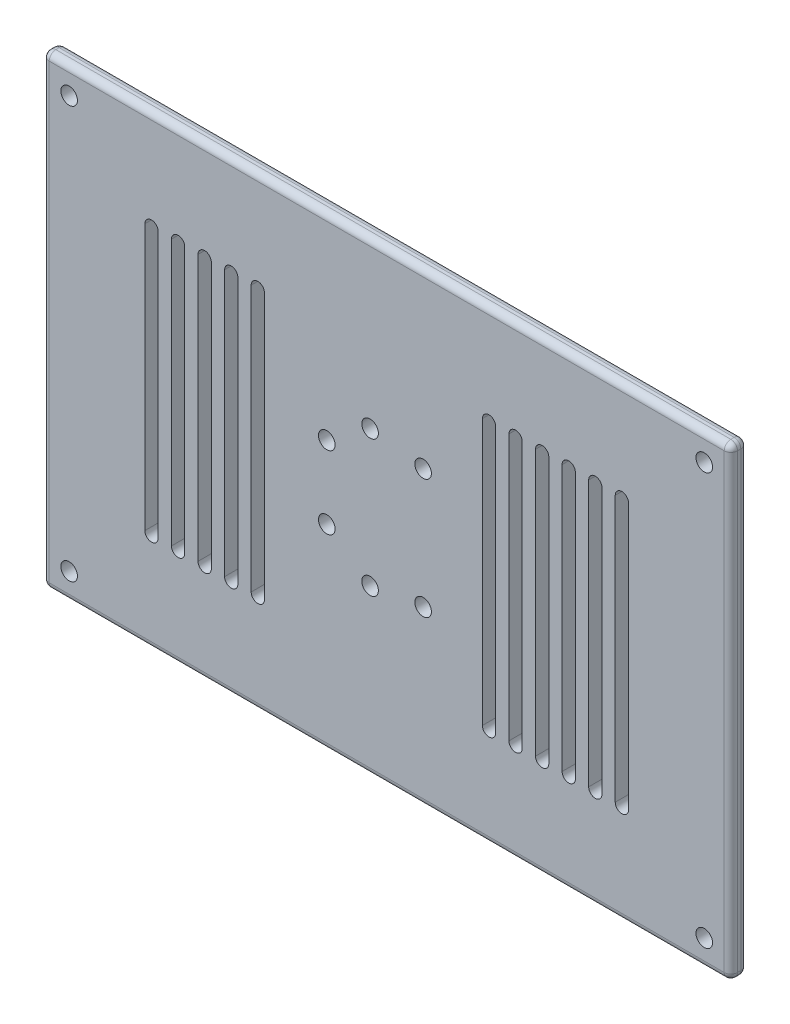
SolidWorks part; units mm, degrees
ref_plane "Plan de face" through (0, 0, 0) normal (0, 0, 1) x (1, 0, 0)
ref_plane "Plan de dessus" through (0, 0, 0) normal (0, 1, 0) x (1, 0, 0)
ref_plane "Plan de droite" through (0, 0, 0) normal (1, 0, 0) x (0, 0, -1)
sketch "Esquisse1" plane through (0, 0, 0) normal (0, 0, 1) x (1, 0, 0)
  line L1 (-51.8, 35) -> (51.8, 35)
  line L2 (-51.8, 35) -> (-51.8, -35)
  line L3 (-51.8, -35) -> (51.8, -35)
  line L4 (51.8, 35) -> (51.8, -35)
  line L5 (-51.8, 35) -> (51.8, -35) construction
  line L6 (-51.8, -35) -> (51.8, 35) construction
  point P0 (0, 0)
  point P5 (0, 0)
  point P13 (0, 0)
  dimension "D1" = 70
  dimension "D2" = 103.6
extrude "Boss.-Extru.1" add sketch "Esquisse1" along normal blind 2.5
sketch "Esquisse17" plane through (0, 0, 2.5) normal (0, 0, 1) x (1, 0, 0)
  line L1 (-2.5, 10.25) -> (2.5, 10.25)
  line L2 (-2.5, 10.25) -> (-2.5, -10.25) construction
  line L3 (-2.5, -10.25) -> (2.5, -10.25)
  line L4 (2.5, 10.25) -> (2.5, -10.25)
  line L5 (-2.5, 10.25) -> (2.5, -10.25) construction
  line L6 (-2.5, -10.25) -> (2.5, 10.25) construction
  circle A0 centre (-2.5, 10.25) radius 3
  circle A1 centre (-2.5, -10.25) radius 3
  point P0 (0, 0)
  point P9 (-2.5, -10.25)
  point P10 (-2.5, 10.25)
  dimension "D1" = 20.5
  dimension "D2" = 5
fillet "Congé3" radius 1 12 edges at (-51.8, 0, 2.5) (0, -35, 2.5) (0, 35, 2.5) (51.8, 0, 2.5) (51.8, -35, 1.25) (51.8, 35, 1.25) (-51.8, 35, 1.25) (-51.8, -35, 1.25) (51.8, 0, 0) (0, 35, 0) (-51.8, 0, 0) (0, -35, 0)
extrude "Boss.-Extru.12" add sketch "Esquisse17" against normal blind 7 contours A1 | A0
sketch "Esquisse40" plane through (0, 0, 2.5) normal (0, 0, 1) x (1, 0, 0)
  line L1 (9.0156, -5.4801) -> (5.4801, -9.0156)
  line L2 (9.0156, -5.4801) -> (-5.4801, 9.0156)
  line L3 (-5.4801, 9.0156) -> (-9.0156, 5.4801)
  line L4 (5.4801, -9.0156) -> (-9.0156, 5.4801)
  line L5 (2.5, -10.25) -> (-2.5, 10.25) construction
  line L6 (2.5, 10.25) -> (-2.5, -10.25) construction
  circle A0 centre (5.4801, -9.0156) radius 3
  circle A1 centre (-9.0156, 5.4801) radius 3
  point P0 (0, 0)
  dimension "D1" = 5
  dimension "D2" = 20.5
extrude "Boss.-Extru.8" add sketch "Esquisse40" against normal blind 7 contours A1 | A0
sketch "Esquisse42" plane through (0, 0, 2.5) normal (0, 0, 1) x (1, 0, 0)
  line L5 (-5.4801, -9.0156) -> (-9.0156, -5.4801)
  line L6 (-5.4801, -9.0156) -> (9.0156, 5.4801)
  line L7 (9.0156, 5.4801) -> (5.4801, 9.0156)
  line L8 (-9.0156, -5.4801) -> (5.4801, 9.0156)
  line L9 (2.5, -10.25) -> (-2.5, 10.25) construction
  line L10 (2.5, 10.25) -> (-2.5, -10.25) construction
  circle A0 centre (-9.0156, -5.4801) radius 3
  circle A1 centre (5.4801, 9.0156) radius 3
  point P0 (0, 0)
  dimension "D1" = 5
  dimension "D2" = 20.5
extrude "Boss.-Extru.10" add sketch "Esquisse42" against normal blind 7 contours A1 | A0
sketch "Esquisse36" plane through (0, 0, 2.5) normal (0, 0, 1) x (1, 0, 0)
  line L0 (25.4, 0) -> (0, 0) construction
  line L1 (50.8, -34) -> (50.8, 34) construction
  line L2 (50.8, 0) -> (25.4, 0) construction
  line L4 (35.4, -20) -> (15.4, -20) construction
  line L5 (35.4, -20) -> (35.4, 20) construction
  line L6 (35.4, 20) -> (15.4, 20) construction
  line L7 (15.4, -20) -> (15.4, 20) construction
  line L8 (35.4, -20) -> (15.4, 20) construction
  line L9 (35.4, 20) -> (15.4, -20) construction
  line L10 (35.4, 20) -> (35.4, -20) construction
  line L11 (36.4, 20) -> (36.4, -20)
  line L12 (34.4, 20) -> (34.4, -20)
  arc A0 (36.4, 20) -> (34.4, 20) centre (35.4, 20) ccw
  arc A1 (34.4, -20) -> (36.4, -20) centre (35.4, -20) ccw
  point P0 (25.4, 0)
  point P8 (35.4, 0)
  dimension "D1" = 20
  dimension "D2" = 40
extrude "Enlèv. mat.-Extru.2" cut sketch "Esquisse36" against normal through all
pattern_linear "Répétition linéaire1" count 6 spacing 4 along (-1, 0, 0) of "Enlèv. mat.-Extru.2"
sketch "Esquisse37" plane through (0, 0, 2.5) normal (0, 0, 1) x (1, 0, 0)
  line L0 (0, 0) -> (-50.8, 0) construction
  line L1 (-50.8, 34) -> (-50.8, -34) construction
  line L2 (-35.4, 20) -> (-35.4, -20) construction
  line L3 (-15.4, 20) -> (-35.4, 20) construction
  line L4 (-15.4, 20) -> (-15.4, -20) construction
  line L5 (-15.4, -20) -> (-35.4, -20) construction
  line L6 (-35.4, 20) -> (-35.4, -20) construction
  line L7 (-15.4, 20) -> (-35.4, -20) construction
  line L8 (-15.4, -20) -> (-35.4, 20) construction
  line L9 (-34.4, 20) -> (-34.4, -20)
  line L10 (-36.4, 20) -> (-36.4, -20)
  arc A0 (-34.4, 20) -> (-36.4, 20) centre (-35.4, 20) ccw
  arc A1 (-36.4, -20) -> (-34.4, -20) centre (-35.4, -20) ccw
  point P5 (-25.4, 0)
  point P11 (-35.4, 0)
  dimension "D1" = 40
  dimension "D2" = 20
extrude "Enlèv. mat.-Extru.3" cut sketch "Esquisse37" against normal through all
pattern_linear "Répétition linéaire2" count 5 spacing 4 along (1, 0, 0) of "Enlèv. mat.-Extru.3"
hole_wizard "Trou pour taraudage pour trou taraudé M38" positions "Esquisse3D10" profile "Esquisse41" hole size "M3" standard "AS"
sketch3d "Esquisse3D10"
  point P0 (5.4801, -9.0156, 2.5)
  point P3 (-9.0156, 5.4801, 2.5)
sketch "Esquisse41" plane through (5.4801, -9.0156, 2.5) normal (1, 0, 0) x (0, -1, 0)
  line L0 (0, 0) -> (0, 5.7511)
  line L1 (0, 5.7511) -> (1.25, 5)
  line L2 (1.25, 5) -> (1.25, 0)
  line L5 (1.25, 0) -> (0, 0)
  line L10 (0, 5.7511) -> (-1.25, 5) construction
  line L11 (0, -6.35) -> (0, 107.95) construction
  dimension "Diamètre du perçage" = 2.5
  dimension "Profondeur du perçage" = 5
  dimension "Angle de pointe" = 118
hole_wizard "Trou pour taraudage pour trou taraudé M39" positions "Esquisse3D11" profile "Esquisse43" hole size "M3" standard "AS"
sketch3d "Esquisse3D11"
  point P0 (5.4801, 9.0156, 2.5)
  point P3 (-9.0156, -5.4801, 2.5)
sketch "Esquisse43" plane through (5.4801, 9.0156, 2.5) normal (1, 0, 0) x (0, -1, 0)
  line L0 (0, 0) -> (0, 5.7511)
  line L1 (0, 5.7511) -> (1.25, 5)
  line L2 (1.25, 5) -> (1.25, 0)
  line L5 (1.25, 0) -> (0, 0)
  line L10 (0, 5.7511) -> (-1.25, 5) construction
  line L11 (0, -6.35) -> (0, 107.95) construction
  dimension "Diamètre du perçage" = 2.5
  dimension "Profondeur du perçage" = 5
  dimension "Angle de pointe" = 118
hole_wizard "Trou pour taraudage pour trou taraudé M311" positions "Esquisse3D15" profile "Esquisse47" hole size "M3" standard "AS"
sketch3d "Esquisse3D15"
  point P0 (-2.5, 10.25, 2.5)
  point P3 (-2.5, -10.25, 2.5)
sketch "Esquisse47" plane through (-2.5, 10.25, 2.5) normal (1, 0, 0) x (0, -1, 0)
  line L0 (0, 0) -> (0, 5.7511)
  line L1 (0, 5.7511) -> (1.25, 5)
  line L2 (1.25, 5) -> (1.25, 0)
  line L5 (1.25, 0) -> (0, 0)
  line L10 (0, 5.7511) -> (-1.25, 5) construction
  line L11 (0, -6.35) -> (0, 107.95) construction
  dimension "Diamètre du perçage" = 2.5
  dimension "Profondeur du perçage" = 5
  dimension "Angle de pointe" = 118
fillet "Congé4" radius 0.5 12 edges at (0.5, -10.25, 0) (0.5, -10.25, -4.5) (0.5, 10.25, 0) (0.5, 10.25, -4.5) (8.4801, -9.0156, -4.5) (8.4801, 9.0156, -4.5) (-6.0156, 5.4801, 0) (-6.0156, 5.4801, -4.5) (-6.0156, -5.4801, 0) (-6.0156, -5.4801, -4.5) (8.4801, 9.0156, 0) (8.4801, -9.0156, 0)
sketch "Esquisse48" plane through (0, 0, 2.5) normal (0, 0, 1) x (1, 0, 0)
  line L0 (51.8, 34) -> (51.8, -34) construction
  line L1 (-50.8, 35) -> (50.8, 35) construction
  line L2 (50.8, -35) -> (-50.8, -35) construction
  line L3 (-50.8, -35) -> (50.8, -35) construction
  line L6 (-51.8, -34) -> (-51.8, 34) construction
  circle A0 centre (-47.8, 31) radius 3
  circle A1 centre (-47.8, -31) radius 3
  circle A2 centre (47.8, 31) radius 3.3164
  circle A3 centre (47.8, -31) radius 3.4515
  dimension "D1" = 4
  dimension "D2" = 4
  dimension "D3" = 4
  dimension "D4" = 4
  dimension "D5" = 4
  dimension "D6" = 4
  dimension "D7" = 4
  dimension "D8" = 4
hole_wizard "Trou pour taraudage pour trou taraudé M312" positions "Esquisse3D16" profile "Esquisse49" hole size "M3" standard "AS"
sketch3d "Esquisse3D16"
  point P0 (-47.8, 31, 2.5)
  point P3 (-47.8, -31, 2.5)
  point P6 (47.8, -31, 2.5)
  point P9 (47.8, 31, 2.5)
sketch "Esquisse49" plane through (-47.8, 31, 2.5) normal (1, 0, 0) x (0, -1, 0)
  line L0 (0, 0) -> (0, 5.7511)
  line L1 (0, 5.7511) -> (1.25, 5)
  line L2 (1.25, 5) -> (1.25, 0)
  line L5 (1.25, 0) -> (0, 0)
  line L10 (0, 5.7511) -> (-1.25, 5) construction
  line L11 (0, -6.35) -> (0, 107.95) construction
  dimension "Diamètre du perçage" = 2.5
  dimension "Profondeur du perçage" = 5
  dimension "Angle de pointe" = 118
